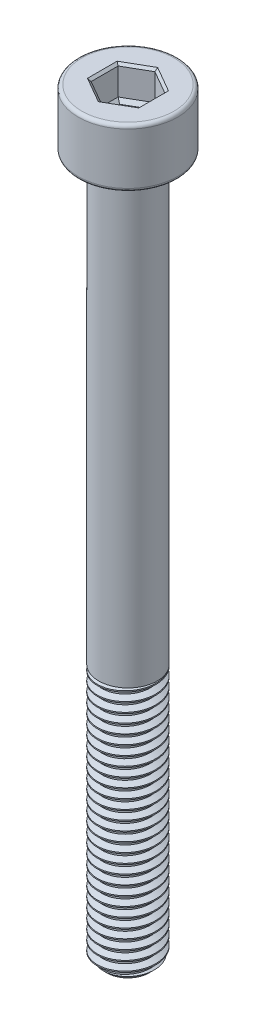
SolidWorks part; units mm, degrees
material "AISI Type A2 Tool Steel"
ref_plane "Front Plane" through (0, 0, 0) normal (0, 0, 1) x (1, 0, 0)
ref_plane "Top Plane" through (0, 0, 0) normal (0, 1, 0) x (1, 0, 0)
ref_plane "Right Plane" through (0, 0, 0) normal (1, 0, 0) x (0, 0, -1)
sketch "Sketch1" plane through (0, 0, 0) normal (0, 1, 0) x (1, 0, 0)
  circle A0 centre (0, 0) radius 2.5
  dimension "D1" = 5
extrude "Boss-Extrude1" add sketch "Sketch1" along normal blind 22
thread "Thread1" pitch 0.8 start angle 0, offset 1, length 0, pitch 0.8, diameter 5
ref_plane "Plane1" through (-2.5, 23, 0) normal (0, 0, 1) x (-1, 0, 0)
sketch "Thread Profile1" plane through (-2.5, 23, 0) normal (0, 0, 1) x (-1, 0, 0)
  line L0 (0, 0) -> (0, 0.8) construction
  line L11 (0, 0) -> (0, 0.7)
  line L12 (0, 0.7) -> (-0.433, 0.45)
  line L13 (-0.433, 0.45) -> (-0.433, 0.25)
  line L15 (-0.433, 0.25) -> (0, 0)
  line L17 (-0.433, 0.35) -> (0, 0.35) construction
  point P2 (0, 0)
  dimension "Pitch" = 0.8
  dimension "Profile_Angle" = 60
  dimension "Profile_Land" = 0.2
  dimension "Profile_Height" = 0.433
sketch "Sketch2" plane through (0, 22, 0) normal (0, 1, 0) x (1, 0, 0)
  circle A0 centre (0, 0) radius 2.5
  dimension "D1" = 5
extrude "Boss-Extrude2" add sketch "Sketch2" along normal blind 38
sketch "Sketch3" plane through (0, 60, 0) normal (0, 1, 0) x (1, 0, 0)
  circle A0 centre (0, 0) radius 4.25
  dimension "D1" = 8.5
extrude "Boss-Extrude3" add sketch "Sketch3" along normal blind 5
fillet "Fillet1" radius 0.3 2 edges at (0, 60, 4.25) (0, 65, 4.25)
sketch "Sketch4" plane through (0, 0, 0) normal (0, 0, 1) x (1, 0, 0)
  line L0 (0, 0) -> (0, 0.4416) construction
  line L1 (0, 0) -> (2.51, 0) construction
  line L2 (2.51, 0) -> (2.51, 0.7)
  line L3 (2.51, 0.7) -> (1.81, 0)
  line L4 (1.81, 0) -> (2.51, 0)
  dimension "D1" = 0.7
  dimension "D2" = 45
  dimension "D3" = 2.51
revolve "Cut-Revolve1" cut sketch "Sketch4" angle 360 about L0
sketch "Sketch5" plane through (0, 65, 0) normal (0, 1, 0) x (1, 0, 0)
  line L1 (0, 2.3094) -> (-2, 1.1547)
  line L2 (-2, 1.1547) -> (-2, -1.1547)
  line L3 (-2, -1.1547) -> (0, -2.3094)
  line L4 (0, -2.3094) -> (2, -1.1547)
  line L5 (2, -1.1547) -> (2, 1.1547)
  line L6 (2, 1.1547) -> (0, 2.3094)
  circle A0 centre (0, 0) radius 2 construction
  dimension "D1" = 4
extrude "Cut-Extrude1" cut sketch "Sketch5" against normal blind 2.5
chamfer "Chamfer1" distance 0.2 angle 45 6 edges at (-1, 65, 1.7321) (1, 65, 1.7321) (2, 65, 0) (1, 65, -1.7321) (-1, 65, -1.7321) (-2, 65, 0)
sketch "Sketch6" plane through (0, 62.5, 0) normal (0, 1, 0) x (1, 0, 0)
  line L1 (0, 2.3094) -> (-2, 1.1547)
  line L2 (-2, 1.1547) -> (-2, -1.1547)
  line L3 (-2, -1.1547) -> (0, -2.3094)
  line L4 (0, -2.3094) -> (2, -1.1547)
  line L5 (2, -1.1547) -> (2, 1.1547)
  line L6 (2, 1.1547) -> (0, 2.3094)
  circle A0 centre (0, 0) radius 2 construction
extrude "Cut-Extrude2" cut sketch "Sketch6" against normal blind 0.3 draft 45
